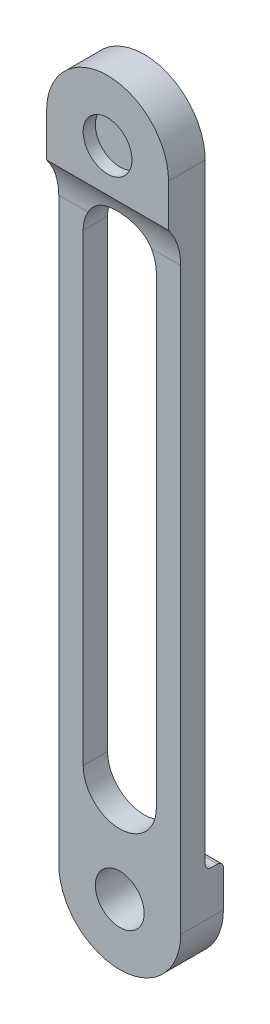
SolidWorks part; units mm, degrees
material "PLA"
ref_plane "Alzado" through (0, 0, 0) normal (0, 0, 1) x (1, 0, 0)
ref_plane "Planta" through (0, 0, 0) normal (0, 1, 0) x (1, 0, 0)
ref_plane "Vista lateral" through (0, 0, 0) normal (1, 0, 0) x (0, 0, -1)
sketch "Croquis1" plane through (0, 0, 0) normal (0, 0, 1) x (1, 0, 0)
  line L0 (0, 54) -> (0, -54) construction
  line L1 (10, 54) -> (10, -54)
  line L2 (-10, 54) -> (-10, -54)
  line L3 (0, 38) -> (0, -38) construction
  line L4 (6, 38) -> (6, -38)
  line L5 (-6, 38) -> (-6, -38)
  line L6 (-10, -47) -> (10, -47)
  line L7 (0, 50) -> (0, 44) construction
  line L8 (-10, 47) -> (10, 47)
  line L9 (0, -50) -> (0, -44) construction
  arc A0 (10, 54) -> (-10, 54) centre (0, 54) ccw
  arc A1 (-10, -54) -> (10, -54) centre (0, -54) ccw
  circle A2 centre (0, 54) radius 4
  circle A3 centre (0, -54) radius 4
  arc A4 (6, 38) -> (-6, 38) centre (0, 38) ccw
  arc A5 (-6, -38) -> (6, -38) centre (0, -38) ccw
  point P2 (0, 0)
  point P14 (0, 0)
  point P23 (0, 47)
  point P28 (0, -47)
  dimension "D1" = 8
  dimension "D2" = 20
  dimension "D3" = 108
  dimension "D4" = 4
  dimension "D5" = 16
extrude "Saliente-Extruir1" add sketch "Croquis1" along normal blind 4 contours L1 A0 L2 L8 A2 | L2 A1 L1 L8 A5 L5 A4 L4 A3 | L2 A1 L1 A0 | A3 | L5 A5 L4 A4 region at (9.7375, 50.5, 0) region at (9.039, 0, 0)
extrude "Saliente-Extruir2" add sketch "Croquis1<5>" against normal blind 3 contours L2 A1 L1 L6 A3 region at (9.7375, -50.5, 0)
sketch "Croquis1<5>" plane through (0, 0, 0) normal (0, 0, 1) x (1, 0, 0) same geometry as "Croquis1"
fillet "Redondeo2" radius 1 2 edges at (0, -47, -3) (0, -47, 0)
extrude "Saliente-Extruir3" add sketch "Croquis1<6>" along normal blind 6 contours L1 A0 L2 L8 A2 region at (9.7375, 50.5, 0)
sketch "Croquis1<6>" plane through (0, 0, 0) normal (0, 0, 1) x (1, 0, 0) same geometry as "Croquis1"
fillet "Redondeo1" radius 10 1 edges at (0, 47, 4)
